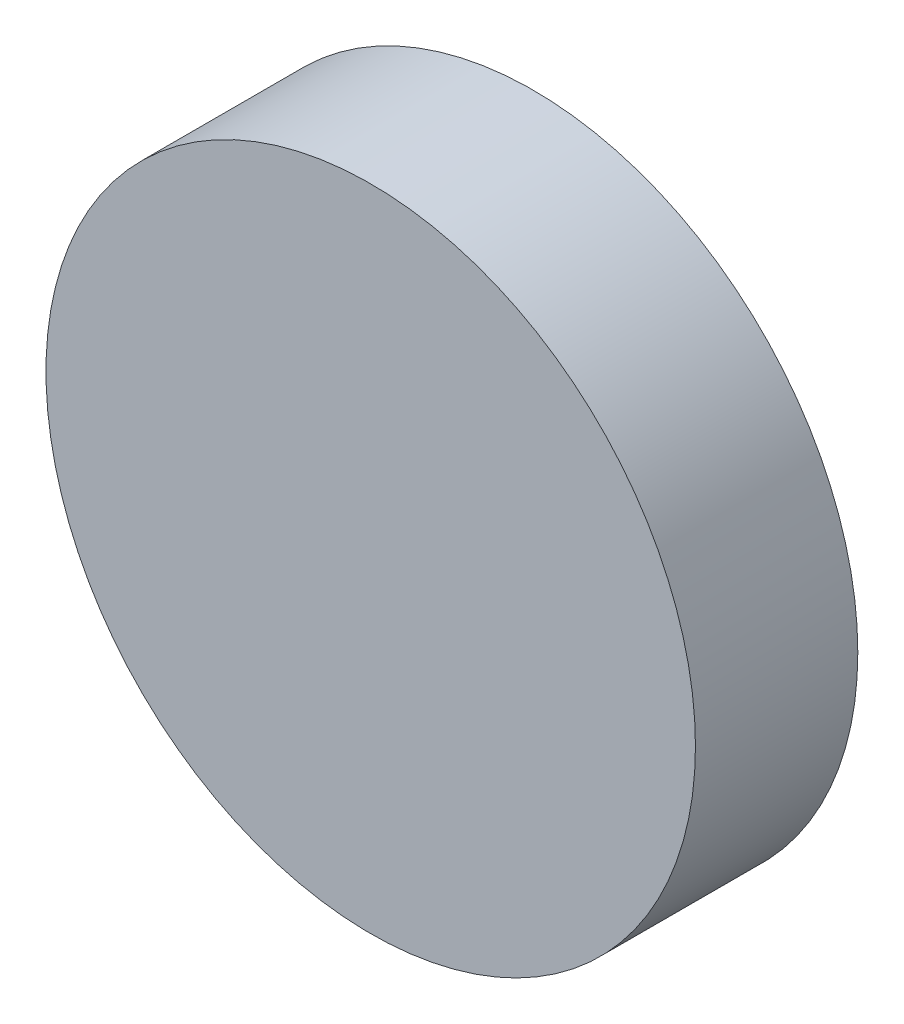
SolidWorks part; units mm, degrees
ref_plane "Front Plane" through (0, 0, 0) normal (0, 0, 1) x (1, 0, 0)
ref_plane "Top Plane" through (0, 0, 0) normal (0, 1, 0) x (1, 0, 0)
ref_plane "Right Plane" through (0, 0, 0) normal (1, 0, 0) x (0, 0, -1)
sketch "Sketch1" plane through (0, 0, 0) normal (0, 0, 1) x (1, 0, 0)
  circle A0 centre (0, 0) radius 1.25
  dimension "D1" = 2.5
extrude "Boss-Extrude1" add sketch "Sketch1" along normal blind 2.5
sketch "Sketch2" plane through (0, 0, 2.5) normal (0, 0, 1) x (1, 0, 0)
  circle A0 centre (0, 0) radius 5
  dimension "D1" = 10
extrude "Boss-Extrude2" add sketch "Sketch2" along normal blind 2.5
scale "Scale1" scale about centroid uniform scaling yes scale factor 0.33
